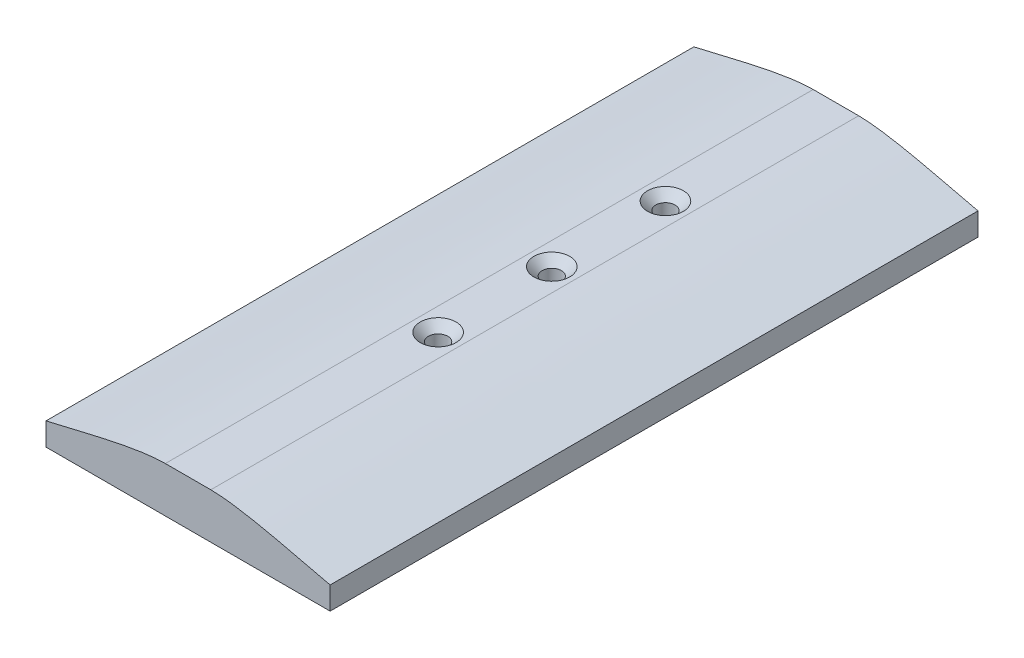
SolidWorks part; units mm, degrees
ref_plane "Front Plane" through (0, 0, 0) normal (0, 0, 1) x (1, 0, 0)
ref_plane "Top Plane" through (0, 0, 0) normal (0, 1, 0) x (1, 0, 0)
ref_plane "Right Plane" through (0, 0, 0) normal (1, 0, 0) x (0, 0, -1)
sketch "Sketch1" plane through (0, 0, 0) normal (0, 1, 0) x (1, 0, 0)
  line L0 (0, 35) -> (0, 25) construction
  line L1 (0, 25) -> (0, 5) construction
  line L2 (0, 5) -> (0, -15) construction
  line L3 (0, -15) -> (0, -35) construction
  line L4 (0, 35) -> (25, 35)
  line L5 (25, 35) -> (25, -35)
  line L6 (25, -35) -> (0, -35)
  line L7 (0, 35) -> (-25, 35)
  line L8 (-25, 35) -> (-25, -35)
  line L9 (-25, -35) -> (0, -35)
  circle A0 centre (0, 25) radius 1.25
  circle A1 centre (0, 5) radius 1.25
  circle A2 centre (0, -15) radius 1.25
  dimension "D1" = 25
  dimension "D2" = 25
extrude "Boss-Extrude1" add sketch "Sketch1" along normal blind 4
sketch "Sketch2" plane through (0, 0, -35) normal (0, 0, -1) x (-1, 0, 0)
  line L0 (0, 4) -> (0, 8) construction
  line L1 (-25, 4) -> (25, 4) construction
  line L2 (0, 8) -> (-4, 8)
  line L3 (-25, 4) -> (25, 4)
  line L4 (0, 8) -> (4, 8)
  spline S0 degree 3 poles (-4, 8) (-9.6522, 8) (-20.3255, 4.9943) (-25, 4) knots 0 0 0 0 1 1 1 1
  spline S1 degree 3 poles (4, 8) (9.6522, 8) (20.3255, 4.9943) (25, 4) knots 0 0 0 0 1 1 1 1
  dimension "D1" = 4
  dimension "D2" = 4
extrude "Boss-Extrude2" add sketch "Sketch2" against normal blind 70
sketch "Sketch3" plane through (0, 8, 0) normal (0, 1, 0) x (1, 0, 0)
  circle A0 centre (0, 25) radius 1.6
  circle A1 centre (0, 5) radius 1.6
  circle A2 centre (0, -15) radius 1.625
  dimension "D1" = 3.2
  dimension "D2" = 3.2
  dimension "D3" = 3.25
extrude "Cut-Extrude1" cut sketch "Sketch3" against normal blind 70
hole_wizard "CSK for M3 Flat Head Machine Screw1" positions "Sketch4" profile "Sketch5" countersink size "M3" standard "ANSI Metric" end condition through all
sketch "Sketch4" plane through (0, 8, 0) normal (0, 1, 0) x (1, 0, 0)
  point P0 (0, 25)
  point P3 (0, 5)
  point P6 (0, -15)
sketch "Sketch5" plane through (0, 8, -25) normal (1, 0, 0) x (0, 0, 1)
  line L0 (0, 0) -> (0, 8)
  line L1 (0, 8) -> (1.7, 8)
  line L2 (1.7, 8) -> (1.7, 1.45)
  line L3 (1.7, 1.45) -> (3.15, 0)
  line L5 (3.15, 0) -> (0, 0)
  line L6 (-1.7, 1.45) -> (-3.15, 0) construction
  line L11 (0, -6.35) -> (0, 107.95) construction
  dimension "Thru Hole Dia." = 3.4
  dimension "Thru Hole Depth" = 8
  dimension "Near C'Sink Dia." = 6.3
  dimension "Near C'Sink Angle" = 90
sketch "Sketch6" plane through (0, 0, -35) normal (0, 0, -1) x (-1, 0, 0)
  line L4 (-25, 0) -> (25, 0)
  line L5 (25, 0) -> (25, 4)
  line L6 (4, 8) -> (-4, 8)
  line L7 (-25, 4) -> (-25, 0)
  line L8 (-25, 0) -> (25, 0)
  line L9 (25, 0) -> (25, 4)
  line L10 (4, 8) -> (-4, 8)
  line L11 (-25, 4) -> (-25, 0)
  spline S2 degree 3 poles (-4555.7984, 2007.3478) (4792.2686, -2113.8703) (-4732.2099, 2194.1808) (4490.874, -2196.4877) knots -7.00931 -7.00931 -7.00931 -7.00931 8.048016 8.048016 8.048016 8.048016 only from (25, 4) to (4, 8)
  spline S3 degree 3 poles (-4490.8778, -2196.4895) (4732.2005, 2194.1762) (-4792.2451, -2113.8596) (4555.7618, 2007.3317) knots -7.048018 -7.048018 -7.048018 -7.048018 8.009291 8.009291 8.009291 8.009291 only from (-4, 8) to (-25, 4)
  spline S4 degree 3 poles (25, 4) (20.3255, 4.9943) (9.6522, 8) (4, 8) knots 0 0 0 0 1 1 1 1
  spline S5 degree 3 poles (-4, 8) (-9.6522, 8) (-20.3255, 4.9943) (-25, 4) knots 0 0 0 0 1 1 1 1
  dimension "D1" = 0
extrude "Boss-Extrude3" add sketch "Sketch6" along normal blind 20
sketch "Sketch7" plane through (0, 0, 35) normal (0, 0, 1) x (1, 0, 0)
  line L4 (-25, 0) -> (25, 0)
  line L5 (25, 0) -> (25, 4)
  line L6 (4, 8) -> (-4, 8)
  line L7 (-25, 4) -> (-25, 0)
  line L8 (-25, 0) -> (25, 0)
  line L9 (25, 0) -> (25, 4)
  line L10 (4, 8) -> (-4, 8)
  line L11 (-25, 4) -> (-25, 0)
  spline S2 degree 3 poles (-4555.7984, 2007.3478) (4792.2686, -2113.8703) (-4732.2099, 2194.1808) (4490.874, -2196.4877) knots -7.00931 -7.00931 -7.00931 -7.00931 8.048016 8.048016 8.048016 8.048016 only from (25, 4) to (4, 8)
  spline S3 degree 3 poles (-4490.8778, -2196.4895) (4732.2005, 2194.1762) (-4792.2451, -2113.8596) (4555.7618, 2007.3317) knots -7.048018 -7.048018 -7.048018 -7.048018 8.009291 8.009291 8.009291 8.009291 only from (-4, 8) to (-25, 4)
  spline S4 degree 3 poles (25, 4) (20.3255, 4.9943) (9.6522, 8) (4, 8) knots 0 0 0 0 1 1 1 1
  spline S5 degree 3 poles (-4, 8) (-9.6522, 8) (-20.3255, 4.9943) (-25, 4) knots 0 0 0 0 1 1 1 1
  dimension "D1" = 0
extrude "Boss-Extrude4" add sketch "Sketch7" along normal blind 24
